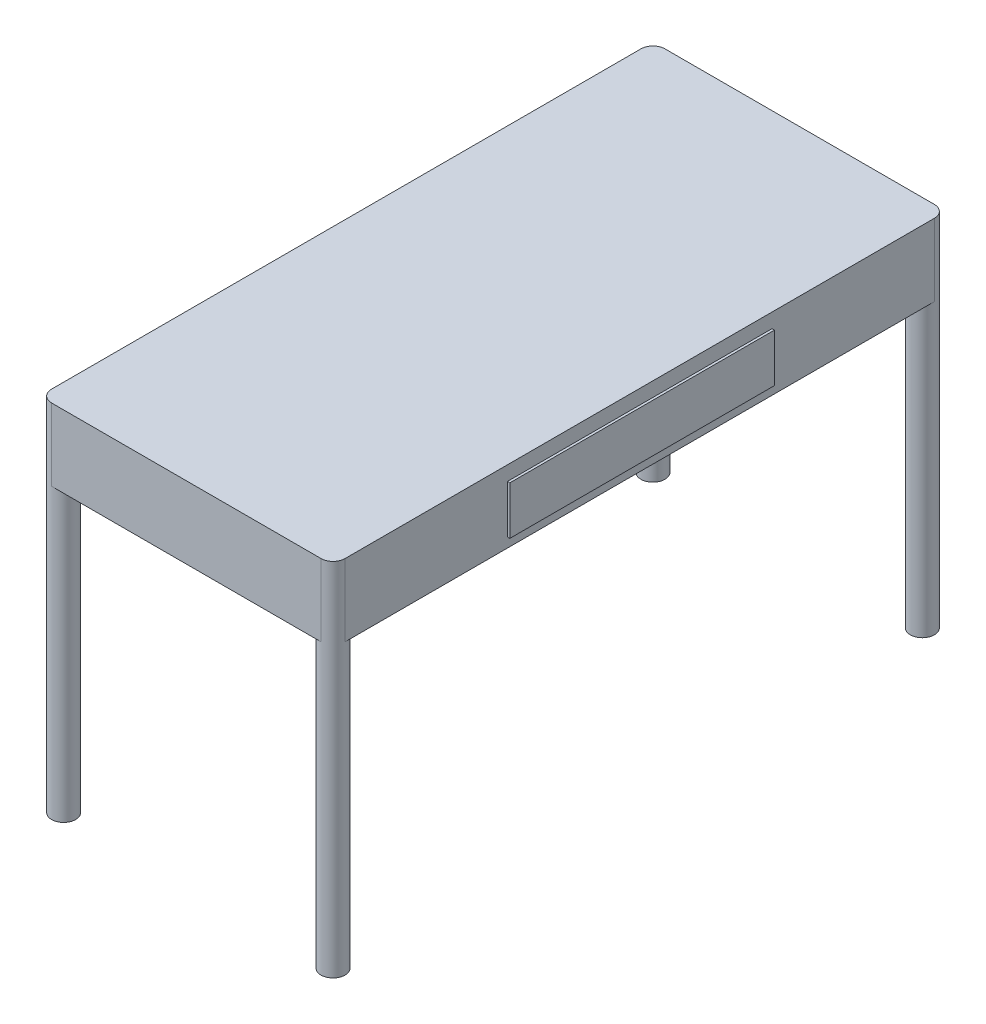
SolidWorks part; units mm, degrees
material "红木"
ref_plane "前视基准面" through (0, 0, 0) normal (0, 0, 1) x (1, 0, 0)
ref_plane "上视基准面" through (0, 0, 0) normal (0, 1, 0) x (1, 0, 0)
ref_plane "右视基准面" through (0, 0, 0) normal (1, 0, 0) x (0, 0, -1)
sketch "草图2" plane through (0, 0, 0) normal (0, 1, 0) x (1, 0, 0)
  line L1 (-305, -637.5) -> (305, -637.5)
  line L2 (-305, -637.5) -> (-305, 637.5)
  line L3 (-305, 637.5) -> (305, 637.5)
  line L4 (305, -637.5) -> (305, 637.5)
  line L5 (-305, -637.5) -> (305, 637.5) construction
  line L6 (-305, 637.5) -> (305, -637.5) construction
  point P0 (0, 0)
  dimension "D1" = 1275
  dimension "D2" = 610
extrude "凸台-拉伸1" add sketch "草图2" against normal blind 150
fillet "圆角1" radius 25 4 edges at (-305, -75, -637.5) (305, -75, -637.5) (-305, -75, 637.5) (305, -75, 637.5)
sketch "草图3" plane through (0, 0, 0) normal (0, 1, 0) x (1, 0, 0)
  circle A0 centre (280, -612.5) radius 25
  arc A1 (280, -637.5) -> (305, -612.5) centre (280, -612.5) ccw construction
extrude "凸台-拉伸2" add sketch "草图3" against normal blind 750
mirror "镜向1" about plane through (0, 0, 0) normal (1, 0, 0) of "凸台-拉伸2"
mirror "镜向2" about plane through (0, 0, 0) normal (0, 0, 1) of "镜向1", "凸台-拉伸2"
sketch "草图4" plane through (305, 0, 0) normal (1, 0, 0) x (0, 0, -1)
  line L0 (-612.5, 0) -> (612.5, 0) construction
  line L1 (-275, -130) -> (275, -130)
  line L2 (-275, -130) -> (-275, -30)
  line L3 (-275, -30) -> (275, -30)
  line L4 (275, -130) -> (275, -30)
  line L5 (-275, -130) -> (275, -30) construction
  line L6 (-275, -30) -> (275, -130) construction
  point P0 (0, -80)
  dimension "D1" = 550
  dimension "D2" = 30
  dimension "D3" = 100
extrude "凸台-拉伸3" add sketch "草图4" along normal blind 5
